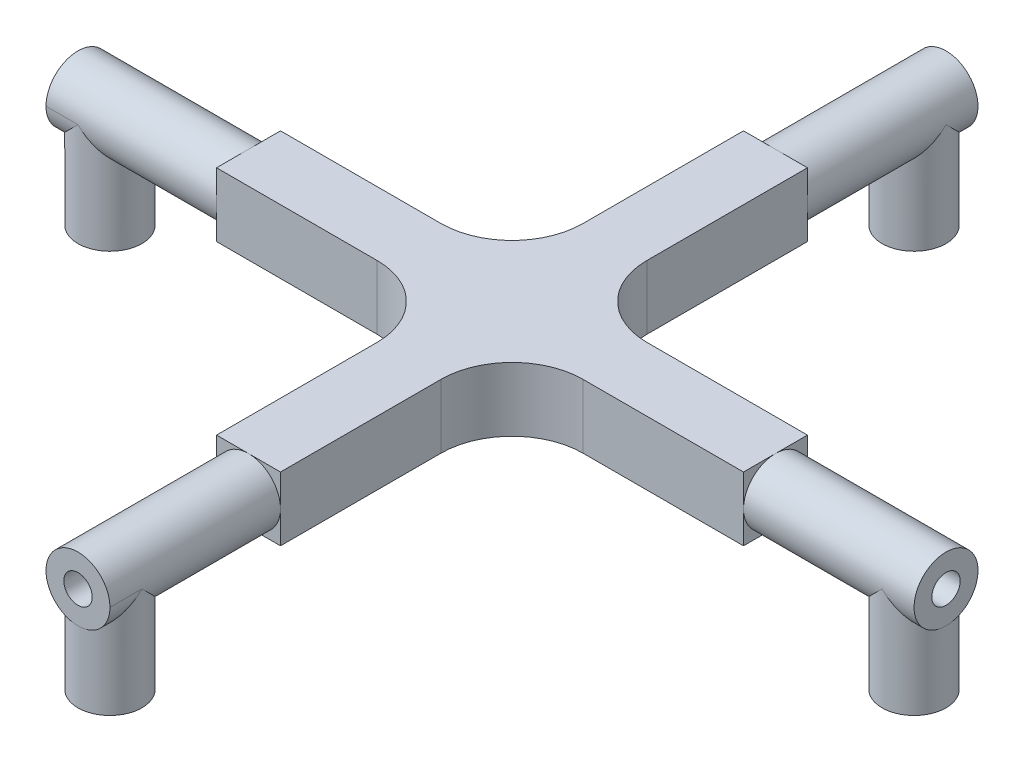
SolidWorks part; units mm, degrees
material "ABS"
ref_plane "Front Plane" through (0, 0, 0) normal (0, 0, 1) x (1, 0, 0)
ref_plane "Top Plane" through (0, 0, 0) normal (0, 1, 0) x (1, 0, 0)
ref_plane "Right Plane" through (0, 0, 0) normal (1, 0, 0) x (0, 0, -1)
sketch "Sketch1" plane through (0, 0, 0) normal (0, 1, 0) x (1, 0, 0)
  line L0 (-2.25, -2.25) -> (-2.25, -30.54)
  line L5 (-2.25, 30.54) -> (2.25, 30.54)
  line L6 (-2.25, 30.54) -> (-2.25, 2.25)
  line L7 (-2.25, -30.54) -> (2.25, -30.54)
  line L8 (2.25, 30.54) -> (2.25, 2.25)
  line L9 (-30.54, 2.25) -> (-2.25, 2.25)
  line L10 (-30.54, 2.25) -> (-30.54, -2.25)
  line L11 (-30.54, -2.25) -> (-2.25, -2.25)
  line L12 (30.54, 2.25) -> (30.54, -2.25)
  line L13 (2.25, -2.25) -> (2.25, -30.54)
  line L14 (2.25, 2.25) -> (30.54, 2.25)
  line L15 (2.25, -2.25) -> (30.54, -2.25)
  line L16 (0, 0) -> (-50000, 0) construction
  line L17 (0, 0) -> (0, 50000) construction
  circle A0 centre (0, 28.2885) radius 2.25 construction
  circle A1 centre (28.28, 0) radius 2.25 construction
  point P4 (0, -30.54)
  point P16 (-30.54, 0)
  dimension "D1" = 4.5
  dimension "D2" = 40
  dimension "D3" = 4.5
  dimension "D4" = 28.2885
  dimension "D5" = 28.29
  dimension "D6" = 28.29
  dimension "D7" = 28.29
  dimension "D8" = 28.29
extrude "Boss-Extrude1" add sketch "Sketch1" along normal blind 4.5
sketch "Sketch7" plane through (0, 0, -30.54) normal (0, 0, -1) x (-1, 0, 0)
  line L0 (-2.25, 4.5) -> (2.25, 4.5) construction
  line L1 (2.25, 4.5) -> (2.25, 0) construction
  circle A0 centre (0, 2.25) radius 2.25
  point P5 (0, 4.5)
  point P9 (2.25, 2.25)
  dimension "D1" = 4.5
extrude "Cut-Extrude6" cut sketch "Sketch7" against normal blind 12 flip side to cut
sketch "Sketch9" plane through (0, 0, 0) normal (0, -1, 0) x (1, 0, 0)
  line L0 (-2.25, -30.54) -> (2.25, -30.54) construction
  circle A0 centre (0, -28.29) radius 2.25
  dimension "D1" = 4.5
extrude "Boss-Extrude4" add sketch "Sketch9" against normal blind 2.25 and the other way blind 5
ref_axis "Axis1" through (0, -5.475, 0) along (0, 1, 0)
pattern_circular "CirPattern1" count 4 over 360 about axis through (0, -5.475, 0) along (0, 1, 0) of "Cut-Extrude6", "Boss-Extrude4"
sketch "Sketch11" plane through (0, 0, -30.54) normal (0, 0, -1) x (-1, 0, 0)
  circle A0 centre (0, 2.25) radius 1
  dimension "D1" = 2
extrude "Cut-Extrude7" cut sketch "Sketch11" against normal blind 10
pattern_circular "CirPattern2" count 4 over 360 about axis through (0, -5.475, 0) along (0, 1, 0) of "Cut-Extrude7"
sketch "Sketch12" plane through (0, -5, 0) normal (0, -1, 0) x (1, 0, 0)
  circle A0 centre (0, -28.29) radius 1
  circle A1 centre (-28.29, 0) radius 1
  circle A2 centre (0, 28.29) radius 1
  circle A3 centre (28.29, 0) radius 1
  dimension "D1" = 2
  dimension "D2" = 2
  dimension "D3" = 2
  dimension "D4" = 2
extrude "Cut-Extrude8" cut sketch "Sketch12" against normal blind 4
fillet "Fillet1" radius 5 4 edges at (-2.25, 2.25, 2.25) (-2.25, 2.25, -2.25) (2.25, 2.25, -2.25) (2.25, 2.25, 2.25)
